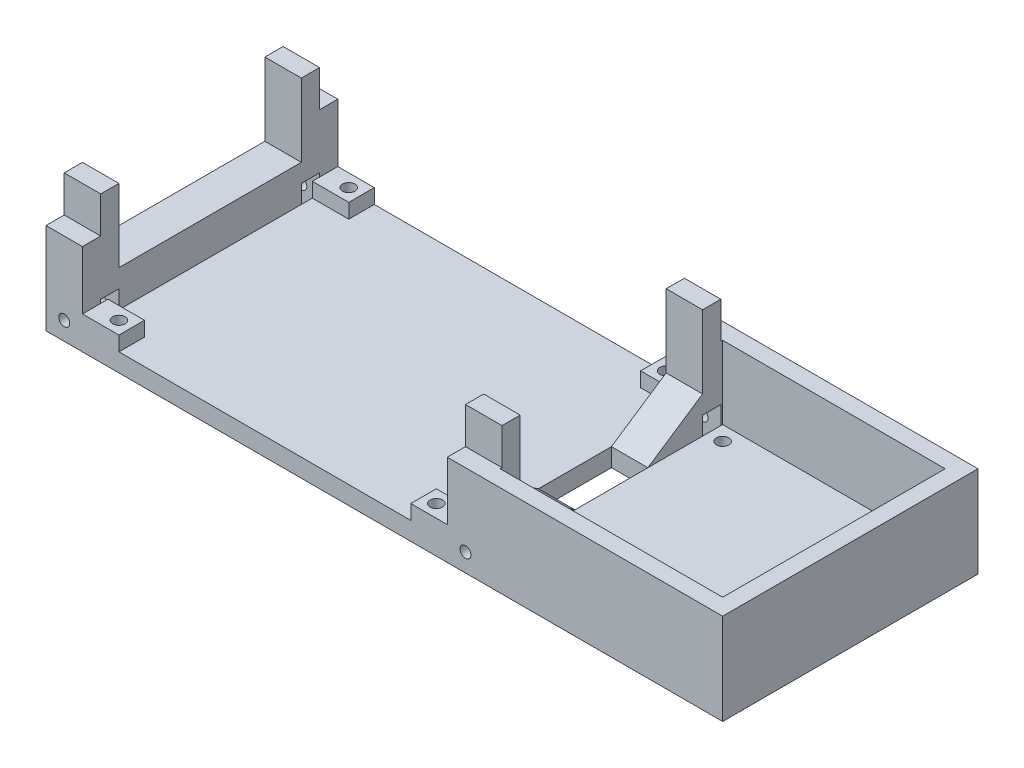
SolidWorks part; units mm, degrees
ref_plane "Front Plane" through (0, 0, 0) normal (0, 0, 1) x (1, 0, 0)
ref_plane "Top Plane" through (0, 0, 0) normal (0, 1, 0) x (1, 0, 0)
ref_plane "Right Plane" through (0, 0, 0) normal (1, 0, 0) x (0, 0, -1)
sketch "Sketch1" plane through (0, 0, 0) normal (0, 1, 0) x (1, 0, 0)
  line L1 (-60, -35) -> (60, -35)
  line L2 (-60, -35) -> (-60, 35)
  line L3 (-60, 35) -> (60, 35)
  line L4 (60, -35) -> (60, 35)
  line L5 (-60, -35) -> (60, 35) construction
  line L6 (-60, 35) -> (60, -35) construction
  point P0 (0, 0)
  dimension "D1" = 120
  dimension "D2" = 70
extrude "Boss-Extrude1" add sketch "Sketch1" along normal blind 5
sketch "Sketch4" plane through (0, 5, 0) normal (0, 1, 0) x (1, 0, 0)
  line L1 (-60, -35) -> (-50, -35)
  line L2 (-60, -35) -> (-60, -25)
  line L3 (-60, -25) -> (-50, -25)
  line L4 (-50, -35) -> (-50, -25)
  line L5 (-60, 35) -> (-50, 35)
  line L6 (-60, 35) -> (-60, 25)
  line L7 (-60, 25) -> (-50, 25)
  line L8 (-50, 35) -> (-50, 25)
  line L9 (60, -35) -> (50, -35)
  line L10 (60, -35) -> (60, -25)
  line L11 (60, -25) -> (50, -25)
  line L12 (50, -35) -> (50, -25)
  line L13 (60, 35) -> (50, 35)
  line L14 (60, 35) -> (60, 25)
  line L15 (60, 25) -> (50, 25)
  line L16 (50, 35) -> (50, 25)
  dimension "D1" = 10
  dimension "D2" = 10
extrude "Boss-Extrude2" add sketch "Sketch4" along normal blind 30
sketch "Sketch5" plane through (0, 0, 0) normal (0, -1, 0) x (1, 0, 0)
  line L0 (-60, -35) -> (-60, 35) construction
  line L1 (-60, -30) -> (-50, -30)
  line L2 (-60, -30) -> (-60, -25)
  line L3 (-60, -25) -> (-50, -25)
  line L4 (-50, -30) -> (-50, -25)
  line L5 (60, 35) -> (60, -35) construction
  line L6 (-60, 30) -> (-50, 30)
  line L7 (-60, 30) -> (-60, 25)
  line L8 (-60, 25) -> (-50, 25)
  line L9 (-50, 30) -> (-50, 25)
  line L10 (60, 30) -> (50, 30)
  line L11 (60, 30) -> (60, 25)
  line L12 (60, 25) -> (50, 25)
  line L13 (50, 30) -> (50, 25)
  line L14 (60, -35) -> (-60, -35) construction
  line L15 (60, -30) -> (50, -30)
  line L16 (60, -30) -> (60, -25)
  line L17 (60, -25) -> (50, -25)
  line L18 (50, -30) -> (50, -25)
  line L19 (-60, 35) -> (60, 35) construction
  dimension "D1" = 10
  dimension "D2" = 5
  dimension "D3" = 5
  dimension "D4" = 5
extrude "Cut-Extrude2" cut sketch "Sketch5" against normal blind 10
sketch "Sketch11" plane through (0, 35, 0) normal (0, 1, 0) x (1, 0, 0)
  line L0 (-50, -35) -> (-50, -25) construction
  line L1 (-60, -35) -> (-50, -35)
  line L2 (-60, -35) -> (-60, -30)
  line L3 (-60, -30) -> (-50, -30)
  line L4 (-50, -35) -> (-50, -30)
  line L5 (60, -35) -> (60, -25) construction
  line L6 (50, -35) -> (60, -35)
  line L7 (50, -35) -> (50, -30)
  line L8 (50, -30) -> (60, -30)
  line L9 (60, -35) -> (60, -30)
  line L10 (60, 25) -> (60, 35) construction
  line L11 (50, 35) -> (60, 35)
  line L12 (50, 35) -> (50, 30)
  line L13 (50, 30) -> (60, 30)
  line L14 (60, 35) -> (60, 30)
  line L15 (-50, 25) -> (-50, 35) construction
  line L16 (-60, 35) -> (-50, 35)
  line L17 (-60, 35) -> (-60, 30)
  line L18 (-60, 30) -> (-50, 30)
  line L19 (-50, 35) -> (-50, 30)
extrude "Cut-Extrude4" cut sketch "Sketch11" against normal blind 10
sketch "Sketch8" plane through (0, 5, 0) normal (0, 1, 0) x (1, 0, 0)
  line L1 (-50, 35) -> (-40, 35)
  line L2 (-50, 35) -> (-50, 28)
  line L3 (-50, 28) -> (-40, 28)
  line L4 (-40, 35) -> (-40, 28)
  line L5 (-50, -35) -> (-40, -35)
  line L6 (-50, -35) -> (-50, -28)
  line L7 (-50, -28) -> (-40, -28)
  line L8 (-40, -35) -> (-40, -28)
  line L9 (50, -35) -> (40, -35)
  line L10 (50, -35) -> (50, -28)
  line L11 (50, -28) -> (40, -28)
  line L12 (40, -35) -> (40, -28)
  line L13 (50, 35) -> (40, 35)
  line L14 (50, 35) -> (50, 28)
  line L15 (50, 28) -> (40, 28)
  line L16 (40, 35) -> (40, 28)
  dimension "D1" = 7
  dimension "D2" = 10
extrude "Boss-Extrude5" add sketch "Sketch8" along normal blind 4
hole_wizard "M3 Clearance Hole2" positions "Sketch10" profile "Sketch9" hole size "M3" standard "ANSI Metric"
sketch "Sketch10" plane through (0, 9, 0) normal (0, 1, 0) x (1, 0, 0)
  line L1 (40, -35) -> (50, -35) construction
  line L2 (-50, -30) -> (-50, -28) construction
  point P0 (-43.5, -31.5)
  point P2 (-43.5, 31.5)
  point P4 (43.5, 31.5)
  point P6 (43.5, -31.5)
  dimension "D1" = 87
  dimension "D2" = 63
  dimension "D3" = 3.5
  dimension "D4" = 6.5
sketch "Sketch9" plane through (-43.5, 9, 31.5) normal (1, 0, 0) x (0, 0, 1)
  line L0 (0, 0) -> (0, 66.0215)
  line L1 (0, 66.0215) -> (1.7, 65)
  line L2 (1.7, 65) -> (1.7, 0)
  line L5 (1.7, 0) -> (0, 0)
  line L10 (0, 66.0215) -> (-1.7, 65) construction
  line L11 (0, -6.35) -> (0, 107.95) construction
  dimension "Hole Dia." = 3.4
  dimension "Hole Depth" = 65
  dimension "Drill Angle" = 118
sketch "Sketch12" plane through (0, 0, 0) normal (0, -1, 0) x (1, 0, 0)
  line L1 (125.5, 35) -> (60, 35)
  line L2 (125.5, 35) -> (125.5, -35)
  line L3 (125.5, -35) -> (60, -35)
  line L4 (60, 35) -> (60, -35)
  line L5 (125.5, 35) -> (60, -35) construction
  line L6 (125.5, -35) -> (60, 35) construction
  line L7 (60, 25) -> (60, -25) construction
  point P0 (92.75, 0)
  dimension "D1" = 65.5
  dimension "D2" = 70
extrude "Boss-Extrude6" add sketch "Sketch12" against normal blind 5
sketch "Sketch13" plane through (0, 5, 0) normal (0, 1, 0) x (1, 0, 0)
  line L1 (60, 35) -> (125.5, 35)
  line L2 (60, 35) -> (60, 30.5)
  line L3 (60, 30.5) -> (121, 30.5)
  line L4 (125.5, -35) -> (125.5, 35)
  line L5 (125.5, 35) -> (125.5, -35) construction
  line L6 (60, -35) -> (125.5, -35)
  line L7 (60, -35) -> (60, -30.5)
  line L8 (60, -30.5) -> (121, -30.5)
  line L11 (121, 30.5) -> (121, -30.5)
  dimension "D1" = 61
  dimension "D2" = 4.5
  dimension "D3" = 4.5
extrude "Boss-Extrude7" add sketch "Sketch13" along normal blind 20
hole_wizard "M3 Clearance Hole3" positions "Sketch15" profile "Sketch14" hole size "M3" standard "ANSI Metric"
sketch "Sketch15" plane through (0, 5, 0) normal (0, 1, 0) x (1, 0, 0)
  line L0 (121, -30.5) -> (60, -30.5) construction
  line L2 (60, -30) -> (60, -25) construction
  point P0 (117, -26.5)
  point P2 (117, 26.5)
  point P4 (64, 26.5)
  point P6 (64, -26.5)
  point P15 (60, -27.5)
  dimension "D1" = 53
  dimension "D2" = 53
  dimension "D3" = 4
  dimension "D4" = 4
sketch "Sketch14" plane through (117, 5, 26.5) normal (1, 0, 0) x (0, 0, 1)
  line L0 (0, 0) -> (0, 66.0215)
  line L1 (0, 66.0215) -> (1.7, 65)
  line L2 (1.7, 65) -> (1.7, 0)
  line L5 (1.7, 0) -> (0, 0)
  line L10 (0, 66.0215) -> (-1.7, 65) construction
  line L11 (0, -6.35) -> (0, 107.95) construction
  dimension "Hole Dia." = 3.4
  dimension "Hole Depth" = 65
  dimension "Drill Angle" = 118
sketch "Sketch24" plane through (0, 5, 0) normal (0, 1, 0) x (1, 0, 0)
  line L1 (-60, 25) -> (-50, 25)
  line L2 (-60, 25) -> (-60, -25)
  line L3 (-60, -25) -> (-50, -25)
  line L4 (-50, 25) -> (-50, -25)
  line L5 (60, -25) -> (50, -25)
  line L6 (60, -25) -> (60, 25)
  line L7 (60, 25) -> (50, 25)
  line L8 (50, -25) -> (50, 25)
extrude "Boss-Extrude10" add sketch "Sketch24" along normal blind 10
sketch "Sketch16" plane through (0, 15, 0) normal (0, 1, 0) x (1, 0, 0)
  line L0 (50, 25) -> (50, -25) construction
  line L1 (60, -10) -> (50, -10)
  line L2 (60, -10) -> (60, 10)
  line L3 (60, 10) -> (50, 10)
  line L4 (50, -10) -> (50, 10)
  line L6 (60, -30) -> (60, -25) construction
  line L9 (60, -25) -> (50, -25) construction
  line L10 (50, 25) -> (60, 25) construction
  dimension "D1" = 15
  dimension "D2" = 15
extrude "Cut-Extrude5" cut sketch "Sketch16" against normal through all
sketch "Sketch22" plane through (0, 0, 35) normal (0, 0, 1) x (1, 0, 0)
  line L0 (-60, 0) -> (125.5, 0) construction
  line L2 (-60, 25) -> (-60, 0) construction
  line L3 (50, 25) -> (50, 9) construction
  circle A0 centre (-55, 5) radius 1.5
  circle A1 centre (55, 5) radius 1.5
  point P8 (-60, 3.3385)
  dimension "D3" = 3
  dimension "D1" = 5
  dimension "D2" = 5
  dimension "D4" = 5
extrude "Cut-Extrude7" cut sketch "Sketch22" against normal blind 20
chamfer "Chamfer2" distance 15 distance2 10 2 edges at (55, 15, 10) (55, 15, -10) first distance on face at (53.75, 15, 17.5) first distance on face at (56.25, 15, -17.5)
sketch "Sketch25" plane through (0, 0, 0) normal (0, -1, 0) x (1, 0, 0)
  line L0 (-60, 25) -> (-50, 25) construction
  line L1 (-57.7, -20) -> (-52.3, -20)
  line L2 (-57.7, -20) -> (-57.7, -17.8)
  line L3 (-57.7, -17.8) -> (-52.3, -17.8)
  line L4 (-52.3, -20) -> (-52.3, -17.8)
  line L5 (52.3, -20) -> (57.7, -20)
  line L6 (52.3, -20) -> (52.3, -18.3898)
  line L7 (52.3, -18.3898) -> (57.7, -18.3898)
  line L8 (57.7, -20) -> (57.7, -18.3898)
  line L9 (52.3, 20) -> (57.7, 20)
  line L10 (52.3, 20) -> (52.3, 17.8)
  line L11 (52.3, 17.8) -> (57.7, 17.8)
  line L12 (57.7, 20) -> (57.7, 17.8)
  line L13 (-57.7, 20) -> (-52.3, 20)
  line L14 (-57.7, 20) -> (-57.7, 17.8)
  line L15 (-57.7, 17.8) -> (-52.3, 17.8)
  line L16 (-52.3, 20) -> (-52.3, 17.8)
  line L17 (-50, -25) -> (-60, -25) construction
  line L18 (-50, -25) -> (-60, -25) construction
  line L23 (55, 25) -> (55, -25) construction
  line L24 (50, 25) -> (60, 25) construction
  line L25 (60, -25) -> (50, -25) construction
  line L26 (-55, 25) -> (-55, -25) construction
  line L27 (-60, 25) -> (-50, 25) construction
  dimension "D1" = 2.2
  dimension "D2" = 5
  dimension "D3" = 5
  dimension "D4" = 5.4
  dimension "D5" = 2.7
  dimension "D6" = 2.7
extrude "Cut-Extrude8" cut sketch "Sketch25" against normal blind 8
sketch "Sketch26" plane through (0, 0, -35) normal (0, 0, -1) x (-1, 0, 0)
  circle A0 centre (-55, 5) radius 1.5
  circle A1 centre (55, 5) radius 1.5
  circle A2 centre (55, 5) radius 1.5 construction
  circle A3 centre (-55, 5) radius 1.5 construction
extrude "Cut-Extrude9" cut sketch "Sketch26" against normal blind 20
equation "\"D5@Sketch25\"=\"D4@Sketch25\"/2"
equation "\"D6@Sketch25\"=\"D5@Sketch25\""
